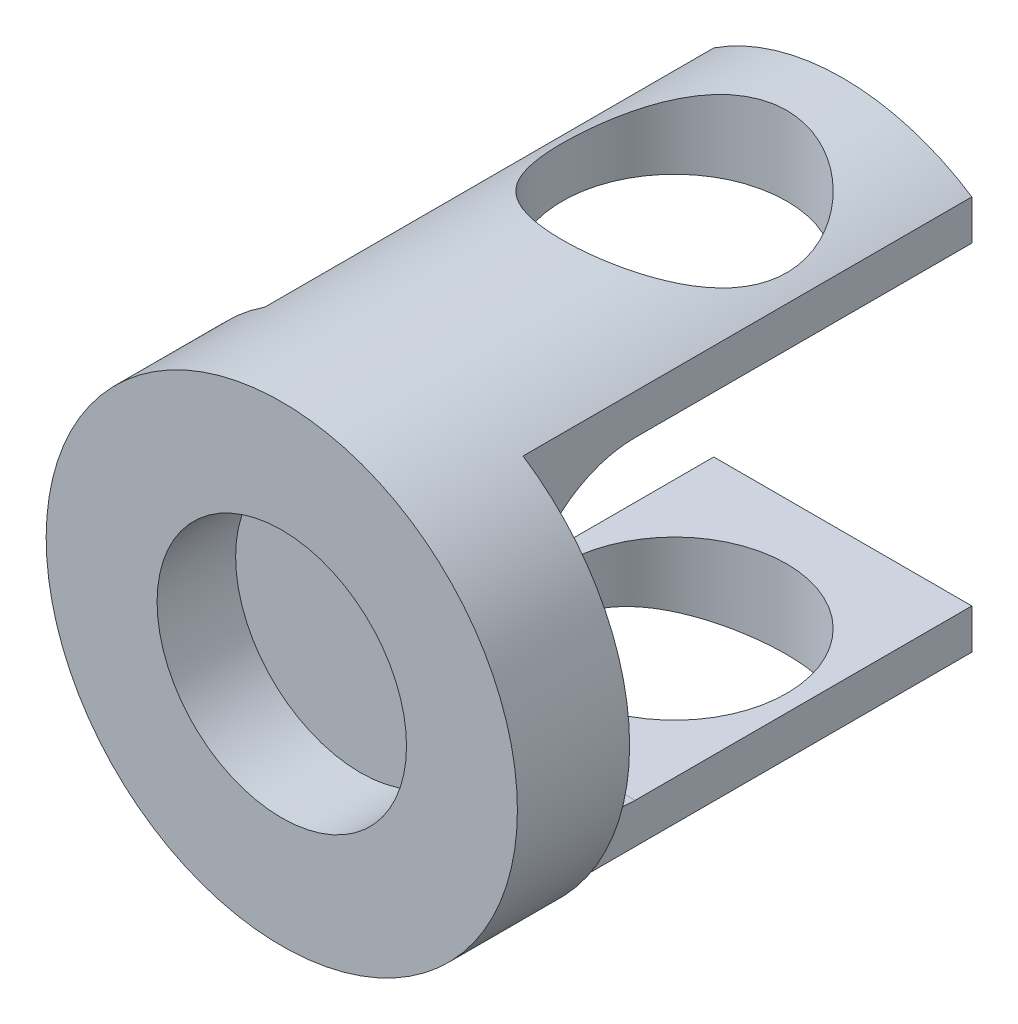
SolidWorks part; units mm, degrees
ref_plane "Płaszczyzna przednia" through (0, 0, 0) normal (0, 0, 1) x (1, 0, 0)
ref_plane "Płaszczyzna górna" through (0, 0, 0) normal (0, 1, 0) x (1, 0, 0)
ref_plane "Płaszczyzna prawa" through (0, 0, 0) normal (1, 0, 0) x (0, 0, -1)
sketch "Szkic1" plane through (0, 0, 0) normal (0, 0, 1) x (1, 0, 0)
  circle A0 centre (0, 0) radius 11.115
  circle A1 centre (0, 0) radius 21
  dimension "D1" = 22.23
  dimension "D2" = 42
extrude "Dodanie-wyciągnięcie1" add sketch "Szkic1" along normal blind 10 contours A1 A0 region at (-20.406, 0, 0)
sketch "Szkic2" plane through (0, 0, 0) normal (0, 0, -1) x (-1, 0, 0)
  line L0 (-11.5, 17.5713) -> (-11.5, 14)
  line L1 (-11.5, 14) -> (11.5, 14)
  line L2 (11.5, 14) -> (11.5, 17.5713)
  line L3 (0, 0) -> (-13.0295, 0) construction
  line L4 (11.5, -14) -> (11.5, -17.5713)
  line L5 (-11.5, -14) -> (11.5, -14)
  line L6 (-11.5, -17.5713) -> (-11.5, -14)
  circle A0 centre (0, 0) radius 21 construction
  arc A1 (-11.5, -17.5713) -> (11.5, -17.5713) centre (0, 0) ccw
  arc A2 (11.5, 17.5713) -> (-11.5, 17.5713) centre (0, 0) ccw
  point P0 (-13.0295, 0)
  point P5 (0, 0)
  dimension "D1" = 14
  dimension "D2" = 23
extrude "Dodanie-wyciągnięcie2" add sketch "Szkic2" along normal blind 40
sketch "Szkic3" plane through (0, 0, 0) normal (0, 0, -1) x (-1, 0, 0)
  circle A0 centre (0, 0) radius 11.115 construction
  circle A1 centre (0, 0) radius 11.115
extrude "Dodanie-wyciągnięcie3" add sketch "Szkic3" against normal blind 3
sketch "Szkic4" plane through (0, -14, 0) normal (0, 1, 0) x (1, 0, 0)
  line L0 (11.5, 40) -> (-11.5, 40) construction
  circle A0 centre (0, 25) radius 10
  dimension "D1" = 20
  dimension "D2" = 15
extrude "Wytnij-wyciągnięcie1" cut sketch "Szkic4" against normal up to next and the other way through all
fillet "Zaokrąglenie1" radius 10 2 edges at (0, -14, 0) (0, 14, 0)
